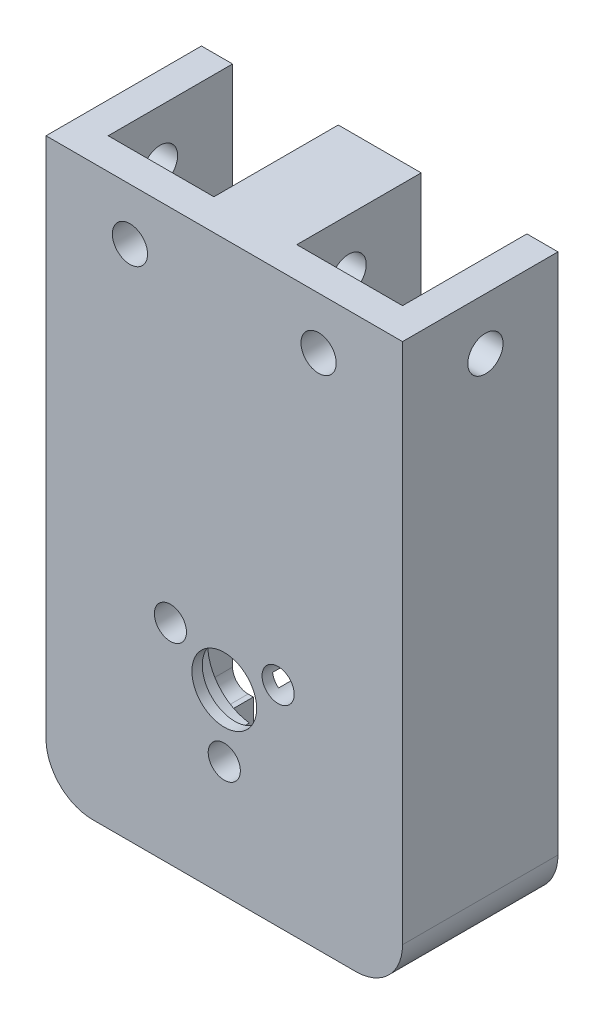
SolidWorks part; units mm, degrees
ref_plane "Front Plane" through (0, 0, 0) normal (0, 0, 1) x (1, 0, 0)
ref_plane "Top Plane" through (0, 0, 0) normal (0, 1, 0) x (1, 0, 0)
ref_plane "Right Plane" through (0, 0, 0) normal (1, 0, 0) x (0, 0, -1)
sketch "Sketch1" plane through (0, 0, 0) normal (0, 0, 1) x (1, 0, 0)
  line L0 (0, 20) -> (0, -20) construction
  line L1 (25, 0) -> (-25, 0) construction
  line L2 (17.2, 1.2765) -> (17.2, 37.7)
  line L3 (17.2, 37.7) -> (14.2, 37.7)
  line L4 (0, 37.7) -> (0, 14.7) construction
  line L5 (0, -14) -> (14.2, -14) construction
  line L6 (-14.2, -14.2) -> (14.2, -14.2)
  line L7 (-17.2, -17.2) -> (17.2, -17.2)
  line L8 (17.2, 1.2765) -> (17.2, -17.2)
  line L9 (14.2, 0) -> (14.2, -14.2)
  line L10 (0, -14) -> (25, -14) construction
  line L11 (0, -14.2) -> (25, -14.2) construction
  line L12 (0, -17.2) -> (25, -17.2) construction
  line L13 (-17.2, 1.2765) -> (-17.2, -17.2)
  line L14 (-14.2, 0) -> (-14.2, -14.2)
  line L15 (-17.2, 1.2765) -> (-17.2, 37.7)
  line L16 (-14.2, 17.7) -> (-4, 17.7)
  line L17 (-14.2, 37.7) -> (-14.2, 17.7)
  line L18 (14.2, 37.7) -> (14.2, 17.7)
  line L19 (-14.2, 37.7) -> (-17.2, 37.7)
  line L20 (0, 17.7) -> (0, 37.7) construction
  line L21 (4, 17.7) -> (4, 37.7)
  line L22 (-4, 17.7) -> (-4, 37.7)
  line L23 (-4, 37.7) -> (4, 37.7)
  line L24 (4, 17.7) -> (14.2, 17.7)
  line L25 (-4, 14.7) -> (-14.2, 14.7)
  line L26 (-14.2, 14.7) -> (-14.2, 0)
  line L27 (4, 14.7) -> (14.2, 14.7)
  line L28 (14.2, 0) -> (14.2, 14.7)
  line L29 (17.2, 12.0941) -> (-17.2, 12.0941) construction
  line L30 (-9.1, 17.7) -> (-9.1, 12.0941) construction
  line L31 (-11.35, 17.7) -> (-11.35, 12.0941) construction
  line L32 (-6.85, 17.7) -> (-6.85, 12.0941) construction
  line L33 (4, 14.7) -> (4, 14.1)
  line L35 (4, 14.1) -> (-4, 14.1)
  line L36 (-4, 14.7) -> (-4, 14.1)
  line L37 (0, 14.7) -> (-4, 14.1) construction
  line L38 (4, 14.1) -> (0, 14.7) construction
  circle A1 centre (0, 0) radius 6 construction
  circle A7 centre (0, 0) radius 14 construction
  arc A9 (0, 17.7) -> (17.2, 1.2765) centre (0.0175, 0.5) cw construction
  point P7 (0, 17.7)
  point P12 (0, 0)
  point P18 (0, 0)
  point P20 (0, 0)
  point P46 (0, 12.0941)
  dimension "D2" = 12
  dimension "D3" = 17.2
  dimension "D6" = 28
  dimension "D8" = 14.2
  dimension "D5" = 20
  dimension "D7" = 25
  dimension "D10" = 10.2
  dimension "D11" = 0.2
  dimension "D13" = 10.2
  dimension "D4" = 14.7
  dimension "D9" = 3
  dimension "D14" = 2.25
  dimension "D16" = 8
  dimension "D17" = 4
  dimension "D18" = 0.6
  dimension "D19" = 20
  dimension "D20" = 54.9
  dimension "D12" = 3
  dimension "D15" = 2.25
extrude "Main Pockets" add sketch "Sketch1" against normal blind 12
sketch "Sketch2" plane through (0, 0, 0) normal (0, 0, 1) x (1, 0, 0)
  line L0 (0, 20) -> (0, -20) construction
  line L1 (-9.1, 17.7) -> (-9.1, 37.7) construction
  line L4 (0, 34) -> (0, 14.2) construction
  line L5 (0, -14) -> (14.2, -14) construction
  line L11 (-17.2, 37.7) -> (-17.2, -17.2)
  line L12 (-17.2, -17.2) -> (17.2, -17.2)
  line L16 (17.2, 37.7) -> (17.2, -17.2)
  line L17 (-4, 17.7) -> (-14.2, 17.7) construction
  line L18 (9.1, 17.7) -> (9.1, 37.7) construction
  line L19 (14.2, 17.7) -> (4, 17.7) construction
  line L21 (-17.2, 32.7) -> (17.2, 32.7) construction
  line L22 (-17.2, 37.7) -> (17.2, 37.7)
  circle A1 centre (0, 0) radius 6 construction
  circle A7 centre (0, 0) radius 14 construction
  arc A9 (0, 17.2) -> (17.2, 0) centre (0, 0) cw construction
  circle A10 centre (0, -6) radius 1.55
  circle A11 centre (-5.1962, 3) radius 1.55
  circle A12 centre (5.1962, 3) radius 1.55
  circle A13 centre (-9.1, 32.7) radius 1.7
  circle A14 centre (9.1, 32.7) radius 1.7
  circle A15 centre (0, 0) radius 3.125
  point P11 (0, 0)
  point P12 (0, 0)
  point P18 (0, 0)
  point P20 (0, 0)
  dimension "D1" = 6.25
  dimension "D2" = 12
  dimension "D3" = 3.1
  dimension "D6" = 28
  dimension "D7" = 3.4
  dimension "D5" = 20
  dimension "D4" = 3
extrude "Mounting Holes" add sketch "Sketch2" along normal blind 3
sketch "Sketch3" plane through (0, 0, 0) normal (0, 0, 1) x (1, 0, 0)
  line L0 (0, 20) -> (0, -20) construction
  line L1 (25, 0) -> (-25, 0) construction
  line L4 (0, 34) -> (0, 14.2) construction
  line L5 (0, -14) -> (14.2, -14) construction
  circle A7 centre (0, 0) radius 14 construction
  arc A9 (0, 17.2) -> (17.2, 0) centre (0, 0) cw construction
  circle A11 centre (0, 0) radius 4.6
  dimension "D2" = 9.2
  dimension "D6" = 28
  dimension "D5" = 20
  dimension "D7" = 25
extrude "Cut-Extrude1" cut sketch "Sketch3" along normal blind 2
sketch "Sketch4" plane through (0, 0, -12) normal (0, 0, -1) x (-1, 0, 0)
  circle A0 centre (-14.2, 17.7) radius 1.5
  circle A1 centre (-4, 17.7) radius 1.5
  circle A2 centre (4, 17.7) radius 1.5
  circle A3 centre (14.2, 17.7) radius 1.5
  dimension "D1" = 3
extrude "Cut-Extrude2" cut sketch "Sketch4" against normal up to surface (12 mm away) up to face at (10.8, 32.7, 0)
sketch "Sketch5" plane through (0, 17.7, 0) normal (0, 1, 0) x (1, 0, 0)
  line L0 (0, 12) -> (0, -3) construction
  line L1 (4, 12) -> (-4, 12) construction
  line L3 (-9.1, 0) -> (-9.1, 12) construction
  line L4 (-12.7, 0) -> (-5.5, 0)
  line L5 (-5.5, 12) -> (-12.7, 12)
  line L6 (-12.7, 0) -> (-5.5, 0) construction
  line L7 (-5.5, 0) -> (-5.5, 12)
  line L9 (-5.5, 12) -> (-12.7, 12) construction
  line L12 (-12.7, 5) -> (-5.5, 5) construction
  line L17 (-5.5, 0) -> (-5.5, 12) construction
  line L18 (-12.7, 12) -> (-12.7, 0)
  line L19 (-12.7, 12) -> (-12.7, 0) construction
  circle A0 centre (-9.1, 5) radius 1.75
  circle A1 centre (9.1, 5) radius 1.75
  dimension "D2" = 3.5
  dimension "D3" = 5
  dimension "D1" = 0
extrude "Cut-Extrude4" cut sketch "Sketch5" against normal up to surface (3 mm away) contours A1 | A0 up to face at (9.1, 14.7, -6)
sketch "Sketch6" plane through (0, -17.2, 0) normal (0, -1, 0) x (1, 0, 0)
  line L0 (12.2, -12) -> (12.2, -2)
  line L1 (12.2, -2) -> (-12.2, -2)
  line L3 (-12.2, -12) -> (12.2, -12)
  line L4 (14.2, 0) -> (4, 0)
  line L5 (4, 0) -> (4, -12)
  line L6 (4, -12) -> (14.2, -12)
  line L7 (14.2, -12) -> (14.2, 0)
  line L10 (4, -12) -> (14.2, -12) construction
  line L11 (14.2, -12) -> (14.2, 0) construction
  line L12 (-14.2, -12) -> (-14.2, 0) construction
  line L13 (-14.2, -12) -> (-14.2, 0) construction
  line L14 (-12.2, -12) -> (-12.2, -2)
  line L15 (12.2, -2) -> (6, -2) construction
  line L16 (4, 0) -> (4, -12) construction
  line L17 (-12.2, -12) -> (-12.2, 0) construction
  line L18 (6, -2) -> (6, -12) construction
  line L23 (14.2, 0) -> (4, 0) construction
  line L24 (14.2, 0) -> (4, 0) construction
  circle A0 centre (-9.1, -5) radius 1.75 construction
  circle A1 centre (9.1, -5) radius 1.75 construction
  circle A2 centre (-9.1, -5) radius 1.75 construction
  circle A3 centre (9.1, -5) radius 1.75 construction
  dimension "D3" = 2
  dimension "D1" = 0
  dimension "Offset" = 2
extrude "Cut-Extrude6" cut sketch "Sketch6" against normal up to surface (3 mm away) up to face at (0, -14.2, -6)
sketch "Sketch8" plane through (17.2, 0, 0) normal (1, 0, 0) x (0, 0, -1)
  line L0 (0, 19.2) -> (0, 37.7) construction
  line L1 (0, 19.2) -> (0, 37.7) construction
  line L2 (-3, 37.7) -> (12, 37.7) construction
  line L3 (5, 19.2) -> (5, 37.7) construction
  line L4 (-3, 32.7) -> (12, 32.7) construction
  circle A0 centre (5, 32.7) radius 1.7
  dimension "D2" = 3.4
  dimension "D1" = 5
extrude "Cut-Extrude7" cut sketch "Sketch8" against normal through all
fillet "Fillet1" radius 1.5 6 edges at (-4, 14.7, -6) (4, 14.7, -6) (-14.2, -14.2, -6) (-14.2, 14.7, -6) (14.2, 14.7, -6) (14.2, -14.2, -6)
fillet "Fillet2" radius 4.5 2 edges at (17.2, -17.2, -4.5) (-17.2, -17.2, -4.5)
fillet "Fillet3" radius 3 2 edges at (-12.2, -15.7, -2) (12.2, -15.7, -2)
